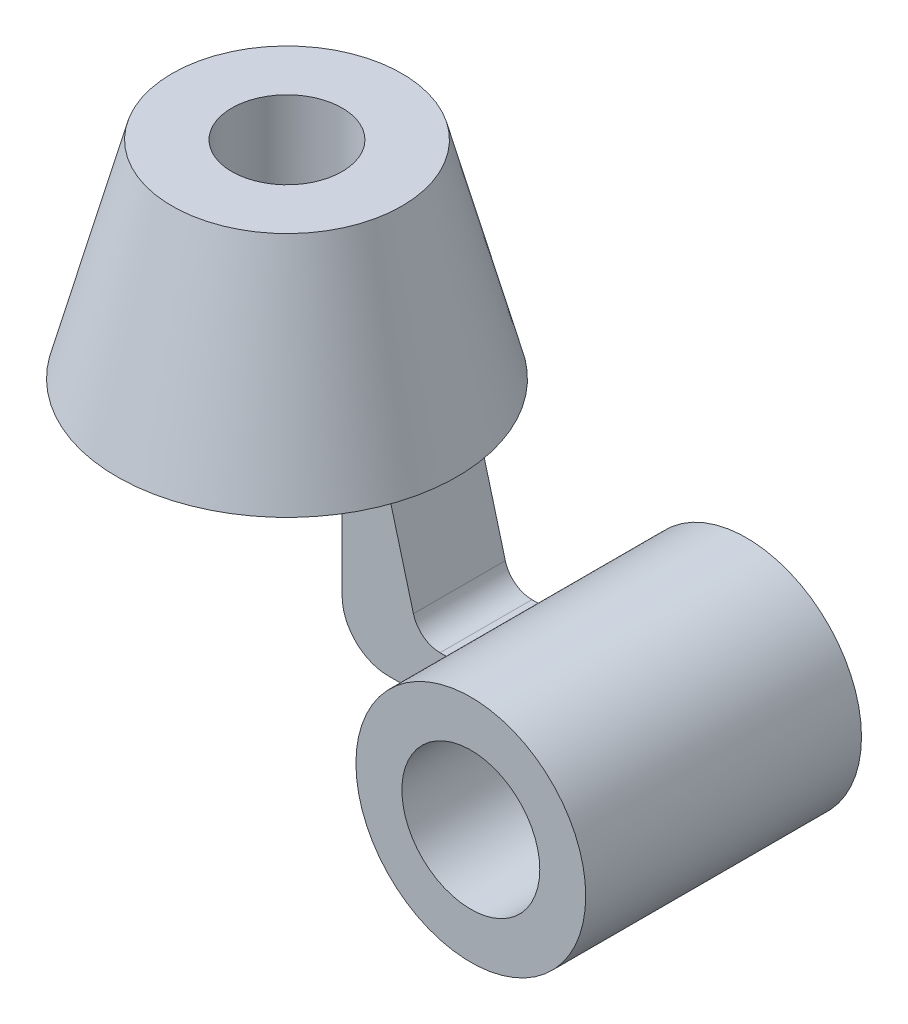
SolidWorks part; units mm, degrees
ref_plane "Front Plane" through (0, 0, 0) normal (0, 0, 1) x (1, 0, 0)
ref_plane "Top Plane" through (0, 0, 0) normal (0, 1, 0) x (1, 0, 0)
ref_plane "Right Plane" through (0, 0, 0) normal (1, 0, 0) x (0, 0, -1)
sketch "Sketch1" plane through (0, 0, 0) normal (0, 0, 1) x (1, 0, 0)
  line L0 (0, 0) -> (37, 0)
  line L1 (37, 0) -> (25, 45)
  line L2 (25, 45) -> (0, 45)
  line L3 (0, 45) -> (0, 0)
  dimension "D1" = 37
  dimension "D2" = 25
  dimension "D3" = 45
revolve "Revolve1" add sketch "Sketch1" angle 360 about L3
sketch "Sketch2" plane through (0, 0, 0) normal (0, 0, 1) x (1, 0, 0)
  line L0 (-37, 0) -> (37, 0) construction
  circle A0 centre (70, -35) radius 25
  dimension "D3" = 50
  dimension "D1" = 35
  dimension "D2" = 70
extrude "Boss-Extrude1" add sketch "Sketch2" along normal blind 30 and the other way blind 30 separate body
sketch "Sketch3" plane through (0, 0, 0) normal (0, 0, 1) x (1, 0, 0)
  line L0 (22, 0) -> (22, -35)
  line L1 (-37, 0) -> (37, 0) construction
  line L2 (22, -35) -> (55.5785, -35)
  line L3 (55.5785, -35) -> (55.5785, -25)
  line L4 (55.5785, -25) -> (38.6987, -25)
  line L5 (38.6987, -25) -> (32, 0)
  line L6 (32, 0) -> (22, 0)
  point P4 (22, -35)
  point P9 (22, -35)
  point P11 (22, -35)
  dimension "D1" = 35
  dimension "D2" = 10
  dimension "D3" = 22
  dimension "D4" = 10
  dimension "D5" = 15
extrude "Boss-Extrude2" add sketch "Sketch3" along normal blind 10 and the other way blind 10
fillet "Fillet1" radius 10 1 edges at (22, -35, 0)
fillet "Fillet2" radius 6 1 edges at (38.6987, -25, 0)
hole_wizard "Ø1.5mm Dowel Hole1" positions "Sketch4" profile "Sketch5" hole size "Ø1.5" standard "ISO" end condition through all
sketch "Sketch4" plane through (0, 45, 0) normal (0, 1, 0) x (1, 0, 0)
  point P0 (0, 0)
sketch "Sketch5" plane through (0, 45, 0) normal (1, 0, 0) x (0, 0, 1)
  line L0 (0, 0) -> (0, 105)
  line L1 (0, 105) -> (12, 105)
  line L2 (12, 105) -> (12, 0)
  line L5 (12, 0) -> (0, 0)
  line L11 (0, -6.35) -> (0, 107.95) construction
  dimension "Thru Hole Dia." = 24
  dimension "Thru Hole Depth" = 105
hole_wizard "Ø1.5mm Dowel Hole2" positions "Sketch6" profile "Sketch7" hole size "Ø1.5" standard "ISO" end condition through all
sketch "Sketch6" plane through (0, 0, 30) normal (0, 0, 1) x (1, 0, 0)
  point P0 (70, -35)
sketch "Sketch7" plane through (70, -35, 30) normal (1, 0, 0) x (0, -1, 0)
  line L0 (0, 0) -> (0, 67)
  line L1 (0, 67) -> (15, 67)
  line L2 (15, 67) -> (15, 0)
  line L5 (15, 0) -> (0, 0)
  line L11 (0, -6.35) -> (0, 107.95) construction
  dimension "Thru Hole Dia." = 30
  dimension "Thru Hole Depth" = 67
